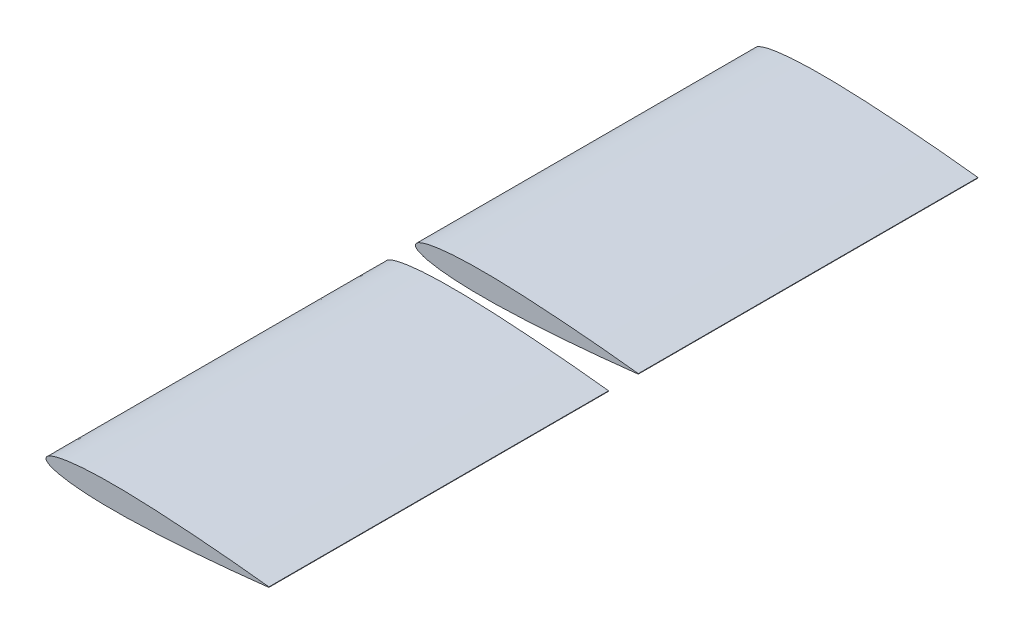
SolidWorks part; units mm, degrees
ref_plane "Спереди" through (0, 0, 0) normal (0, 0, 1) x (1, 0, 0)
ref_plane "Сверху" through (0, 0, 0) normal (0, 1, 0) x (1, 0, 0)
ref_plane "Справа" through (0, 0, 0) normal (1, 0, 0) x (0, 0, -1)
curve "Кривая2"
  spline degree 3 poles (210, 0.2205, 0) (209.4961, 0.2793, 0) (208.0885, 0.4434, 0) (205.5349, 0.7368, 0) (202.1573, 1.1183, 0) (198.2101, 1.5547, 0) (193.8164, 2.0291, 0) (189.059, 2.5297, 0) (184.0003, 3.0477, 0) (178.6905, 3.576, 0) (173.1712, 4.1089, 0) (167.4784, 4.6415, 0) (161.6434, 5.1696, 0) (155.6943, 5.6895, 0) (149.6563, 6.1979, 0) (143.5527, 6.6915, 0) (137.4046, 7.1675, 0) (131.2317, 7.6228, 0) (125.0525, 8.0547, 0) (118.8843, 8.4604, 0) (112.7433, 8.8371, 0) (106.645, 9.1821, 0) (100.604, 9.4927, 0) (94.6343, 9.7665, 0) (88.7492, 10.0009, 0) (82.9617, 10.1936, 0) (77.2839, 10.3425, 0) (71.7277, 10.4456, 0) (66.3046, 10.5012, 0) (61.0256, 10.5081, 0) (55.9013, 10.4648, 0) (50.9422, 10.3709, 0) (46.1583, 10.2257, 0) (41.5593, 10.0293, 0) (37.1549, 9.7819, 0) (32.9541, 9.4841, 0) (28.9661, 9.1368, 0) (25.1997, 8.7415, 0) (21.6633, 8.2995, 0) (18.3654, 7.8128, 0) (15.3141, 7.2834, 0) (12.5174, 6.7136, 0) (9.9828, 6.1055, 0) (7.7177, 5.4617, 0) (5.7292, 4.7844, 0) (4.0231, 4.0756, 0) (2.6063, 3.3369, 0) (1.4778, 2.5676, 0) (0.655, 1.7629, 0) (0.1057, 0.907, 0) (0.0341, 0.2924, 0) (0, 0, 0) knots 0 0 0 0 0.007145 0.019956 0.036196 0.055011 0.075879 0.098429 0.122376 0.147488 0.173572 0.20046 0.228005 0.256076 0.284555 0.313333 0.34231 0.371393 0.400496 0.429538 0.458442 0.487136 0.515552 0.543624 0.57129 0.598491 0.62517 0.651272 0.676746 0.701542 0.725611 0.748908 0.771388 0.793008 0.813728 0.833508 0.85231 0.870097 0.886836 0.902493 0.917037 0.930441 0.94268 0.953734 0.96359 0.972247 0.979722 0.986065 0.991385 0.995901 1 1 1 1
curve "Кривая4"
  spline degree 3 poles (0, 0, 0) (0.0341, -0.2924, 0) (0.1057, -0.907, 0) (0.655, -1.7629, 0) (1.4778, -2.5676, 0) (2.6063, -3.3369, 0) (4.0231, -4.0756, 0) (5.7292, -4.7844, 0) (7.7177, -5.4617, 0) (9.9828, -6.1055, 0) (12.5174, -6.7136, 0) (15.3141, -7.2834, 0) (18.3654, -7.8128, 0) (21.6633, -8.2995, 0) (25.1997, -8.7415, 0) (28.9661, -9.1368, 0) (32.9541, -9.4841, 0) (37.1549, -9.7819, 0) (41.5593, -10.0293, 0) (46.1583, -10.2257, 0) (50.9422, -10.3709, 0) (55.9013, -10.4648, 0) (61.0256, -10.5081, 0) (66.3046, -10.5012, 0) (71.7277, -10.4456, 0) (77.2839, -10.3425, 0) (82.9617, -10.1936, 0) (88.7492, -10.0009, 0) (94.6343, -9.7665, 0) (100.604, -9.4927, 0) (106.645, -9.1821, 0) (112.7433, -8.8371, 0) (118.8843, -8.4604, 0) (125.0525, -8.0547, 0) (131.2317, -7.6228, 0) (137.4046, -7.1675, 0) (143.5527, -6.6915, 0) (149.6563, -6.1979, 0) (155.6943, -5.6895, 0) (161.6434, -5.1696, 0) (167.4784, -4.6415, 0) (173.1712, -4.1089, 0) (178.6905, -3.576, 0) (184.0003, -3.0477, 0) (189.059, -2.5297, 0) (193.8164, -2.0291, 0) (198.2101, -1.5547, 0) (202.1573, -1.1183, 0) (205.5349, -0.7368, 0) (208.0885, -0.4434, 0) (209.4961, -0.2793, 0) (210, -0.2205, 0) knots 0 0 0 0 0.004099 0.008615 0.013935 0.020278 0.027753 0.03641 0.046266 0.05732 0.069559 0.082963 0.097507 0.113164 0.129903 0.14769 0.166492 0.186272 0.206992 0.228612 0.251092 0.274389 0.298458 0.323254 0.348728 0.37483 0.401509 0.42871 0.456376 0.484448 0.512864 0.541558 0.570462 0.599504 0.628607 0.65769 0.686667 0.715445 0.743924 0.771995 0.79954 0.826428 0.852512 0.877624 0.901571 0.924121 0.944989 0.963804 0.980044 0.992855 1 1 1 1
sketch "Эскиз6" plane through (0, 0, 0) normal (0, 0, 1) x (1, 0, 0)
  line L0 (210, 0.2205) -> (210, -0.2205)
  circle A0 centre (42, 0) radius 5
  circle A2 centre (27, 0) radius 5
  circle A3 centre (59, 0) radius 7.5
  circle A4 centre (78, 0) radius 7.5
  circle A5 centre (96, 0) radius 6.5
  circle A6 centre (112, 0) radius 5
  circle A7 centre (127, 0) radius 5
  circle A8 centre (142, 0) radius 5
  circle A9 centre (15, 0) radius 4
  spline S0 degree 3 poles (-2866.9483, -881.3764) (76.8054, 46.1091) (-5.7335, 8.1907) (0.655, -1.7629) (1.4778, -2.5676) (2.6063, -3.3369) (4.0231, -4.0756) (5.7292, -4.7844) (7.7177, -5.4617) (9.9828, -6.1055) (12.5174, -6.7136) (15.3141, -7.2834) (18.3654, -7.8128) (21.6633, -8.2995) (25.1997, -8.7415) (28.9661, -9.1368) (32.9541, -9.4841) (37.1549, -9.7819) (41.5593, -10.0293) (46.1583, -10.2257) (50.9422, -10.3709) (55.9013, -10.4648) (61.0256, -10.5081) (66.3046, -10.5012) (71.7277, -10.4456) (77.2839, -10.3425) (82.9617, -10.1936) (88.7492, -10.0009) (94.6343, -9.7665) (100.604, -9.4927) (106.645, -9.1821) (112.7433, -8.8371) (118.8843, -8.4604) (125.0525, -8.0547) (131.2317, -7.6228) (137.4046, -7.1675) (143.5527, -6.6915) (149.6563, -6.1979) (155.6943, -5.6895) (161.6434, -5.1696) (169.3231, -4.4745) (176.7905, -3.765) (184.0003, -3.0477) (189.059, -2.5297) (193.8164, -2.0291) (198.2101, -1.5547) (202.1573, -1.1183) (205.5349, -0.7368) (314.9698, 11.8352) (421.599, 38.5691) (873.4429, -2915.4445) knots -0.148126 -0.148126 -0.148126 -0.148126 0.004099 0.008615 0.013935 0.020278 0.027753 0.03641 0.046266 0.05732 0.069559 0.082963 0.097507 0.113164 0.129903 0.14769 0.166492 0.186272 0.206992 0.228612 0.251092 0.274389 0.298458 0.323254 0.348728 0.37483 0.401509 0.42871 0.456376 0.484448 0.512864 0.541558 0.570462 0.599504 0.628607 0.65769 0.686667 0.715445 0.743924 0.771995 0.79954 0.852512 0.877624 0.901571 0.924121 0.944989 0.963804 0.980044 0.992855 2.515013 2.515013 2.515013 2.515013 only from (0, 0) to (210, -0.2205) construction
  spline S1 degree 3 poles (873.4362, 2915.401) (421.598, -38.5689) (314.9692, -11.8351) (205.5349, 0.7368) (202.1573, 1.1183) (198.2101, 1.5547) (193.8164, 2.0291) (189.059, 2.5297) (184.0003, 3.0477) (176.7905, 3.765) (169.3231, 4.4745) (161.6434, 5.1696) (155.6943, 5.6895) (149.6563, 6.1979) (143.5527, 6.6915) (137.4046, 7.1675) (131.2317, 7.6228) (125.0525, 8.0547) (118.8843, 8.4604) (112.7433, 8.8371) (106.645, 9.1821) (100.604, 9.4927) (94.6343, 9.7665) (88.7492, 10.0009) (82.9617, 10.1936) (77.2839, 10.3425) (71.7277, 10.4456) (66.3046, 10.5012) (61.0256, 10.5081) (55.9013, 10.4648) (50.9422, 10.3709) (46.1583, 10.2257) (41.5593, 10.0293) (37.1549, 9.7819) (32.9541, 9.4841) (28.9661, 9.1368) (25.1997, 8.7415) (21.6633, 8.2995) (18.3654, 7.8128) (15.3141, 7.2834) (12.5174, 6.7136) (9.9828, 6.1055) (7.7177, 5.4617) (5.7292, 4.7844) (4.0231, 4.0756) (2.6063, 3.3369) (1.4778, 2.5676) (0.655, 1.7629) (-5.7332, -8.1903) (76.7984, -46.1059) (-2866.561, 881.2544) knots -1.515006 -1.515006 -1.515006 -1.515006 0.007145 0.019956 0.036196 0.055011 0.075879 0.098429 0.122376 0.147488 0.20046 0.228005 0.256076 0.284555 0.313333 0.34231 0.371393 0.400496 0.429538 0.458442 0.487136 0.515552 0.543624 0.57129 0.598491 0.62517 0.651272 0.676746 0.701542 0.725611 0.748908 0.771388 0.793008 0.813728 0.833508 0.85231 0.870097 0.886836 0.902493 0.917037 0.930441 0.94268 0.953734 0.96359 0.972247 0.979722 0.986065 0.991385 0.995901 1.148119 1.148119 1.148119 1.148119 only from (210, 0.2205) to (0, 0) construction
  spline S2 degree 3 poles (0, 0) (0.0341, -0.2924) (0.1057, -0.907) (0.655, -1.7629) (1.4778, -2.5676) (2.6063, -3.3369) (4.0231, -4.0756) (5.7292, -4.7844) (7.7177, -5.4617) (9.9828, -6.1055) (12.5174, -6.7136) (15.3141, -7.2834) (18.3654, -7.8128) (21.6633, -8.2995) (25.1997, -8.7415) (28.9661, -9.1368) (32.9541, -9.4841) (37.1549, -9.7819) (41.5593, -10.0293) (46.1583, -10.2257) (50.9422, -10.3709) (55.9013, -10.4648) (61.0256, -10.5081) (66.3046, -10.5012) (71.7277, -10.4456) (77.2839, -10.3425) (82.9617, -10.1936) (88.7492, -10.0009) (94.6343, -9.7665) (100.604, -9.4927) (106.645, -9.1821) (112.7433, -8.8371) (118.8843, -8.4604) (125.0525, -8.0547) (131.2317, -7.6228) (137.4046, -7.1675) (143.5527, -6.6915) (149.6563, -6.1979) (155.6943, -5.6895) (161.6434, -5.1696) (169.3231, -4.4745) (176.7905, -3.765) (184.0003, -3.0477) (189.059, -2.5297) (193.8164, -2.0291) (198.2101, -1.5547) (202.1573, -1.1183) (205.5349, -0.7368) (208.0885, -0.4434) (209.4961, -0.2793) (210, -0.2205) knots 0 0 0 0 0.004099 0.008615 0.013935 0.020278 0.027753 0.03641 0.046266 0.05732 0.069559 0.082963 0.097507 0.113164 0.129903 0.14769 0.166492 0.186272 0.206992 0.228612 0.251092 0.274389 0.298458 0.323254 0.348728 0.37483 0.401509 0.42871 0.456376 0.484448 0.512864 0.541558 0.570462 0.599504 0.628607 0.65769 0.686667 0.715445 0.743924 0.771995 0.79954 0.852512 0.877624 0.901571 0.924121 0.944989 0.963804 0.980044 0.992855 1 1 1 1
  spline S3 degree 3 poles (210, 0.2205) (209.4961, 0.2793) (208.0885, 0.4434) (205.5349, 0.7368) (202.1573, 1.1183) (198.2101, 1.5547) (193.8164, 2.0291) (189.059, 2.5297) (184.0003, 3.0477) (176.7905, 3.765) (169.3231, 4.4745) (161.6434, 5.1696) (155.6943, 5.6895) (149.6563, 6.1979) (143.5527, 6.6915) (137.4046, 7.1675) (131.2317, 7.6228) (125.0525, 8.0547) (118.8843, 8.4604) (112.7433, 8.8371) (106.645, 9.1821) (100.604, 9.4927) (94.6343, 9.7665) (88.7492, 10.0009) (82.9617, 10.1936) (77.2839, 10.3425) (71.7277, 10.4456) (66.3046, 10.5012) (61.0256, 10.5081) (55.9013, 10.4648) (50.9422, 10.3709) (46.1583, 10.2257) (41.5593, 10.0293) (37.1549, 9.7819) (32.9541, 9.4841) (28.9661, 9.1368) (25.1997, 8.7415) (21.6633, 8.2995) (18.3654, 7.8128) (15.3141, 7.2834) (12.5174, 6.7136) (9.9828, 6.1055) (7.7177, 5.4617) (5.7292, 4.7844) (4.0231, 4.0756) (2.6063, 3.3369) (1.4778, 2.5676) (0.655, 1.7629) (0.1057, 0.907) (0.0341, 0.2924) (0, 0) knots 0 0 0 0 0.007145 0.019956 0.036196 0.055011 0.075879 0.098429 0.122376 0.147488 0.20046 0.228005 0.256076 0.284555 0.313333 0.34231 0.371393 0.400496 0.429538 0.458442 0.487136 0.515552 0.543624 0.57129 0.598491 0.62517 0.651272 0.676746 0.701542 0.725611 0.748908 0.771388 0.793008 0.813728 0.833508 0.85231 0.870097 0.886836 0.902493 0.917037 0.930441 0.94268 0.953734 0.96359 0.972247 0.979722 0.986065 0.991385 0.995901 1 1 1 1
  dimension "D1" = 10
  dimension "D3" = 10
  dimension "D4" = 15
  dimension "D5" = 15
  dimension "D6" = 13
  dimension "D7" = 10
  dimension "D15" = 10
  dimension "D16" = 10
  dimension "D17" = 8
  dimension "D2" = 42
  dimension "D8" = 27
  dimension "D9" = 59
  dimension "D10" = 78
  dimension "D11" = 96
  dimension "D12" = 112
  dimension "D13" = 127
  dimension "D14" = 142
  dimension "D18" = 15
ref_plane "л2" through (0, 0, 170) normal (0, 0, 1) x (1, 0, 0)
ref_plane "п2" through (0, 0, -170) normal (0, 0, 1) x (1, 0, 0)
ref_plane "п3" through (0, 0, -334) normal (0, 0, 1) x (1, 0, 0)
ref_plane "л3" through (0, 0, 334) normal (0, 0, 1) x (1, 0, 0)
ref_axis "Ось1" through (0, 0, -345.1687) along (0, 0, 1)
sketch "нерв л2" plane through (0, 0, 170) normal (0, 0, 1) x (1, 0, 0)
  line L0 (210, 0.2205) -> (210, -0.2205)
  circle A0 centre (42, 0) radius 5
  circle A2 centre (27, 0) radius 5
  circle A3 centre (59, 0) radius 7.5
  circle A4 centre (78, 0) radius 7.5
  circle A5 centre (96, 0) radius 6.5
  circle A6 centre (112, 0) radius 5
  circle A7 centre (127, 0) radius 5
  circle A8 centre (142, 0) radius 5
  circle A9 centre (15, 0) radius 4
  spline S2 degree 3 poles (0, 0) (0.0341, -0.2924) (0.1057, -0.907) (0.655, -1.7629) (1.4778, -2.5676) (2.6063, -3.3369) (4.0231, -4.0756) (5.7292, -4.7844) (7.7177, -5.4617) (9.9828, -6.1055) (12.5174, -6.7136) (15.3141, -7.2834) (18.3654, -7.8128) (21.6633, -8.2995) (25.1997, -8.7415) (28.9661, -9.1368) (32.9541, -9.4841) (37.1549, -9.7819) (41.5593, -10.0293) (46.1583, -10.2257) (50.9422, -10.3709) (55.9013, -10.4648) (61.0256, -10.5081) (66.3046, -10.5012) (71.7277, -10.4456) (77.2839, -10.3425) (82.9617, -10.1936) (88.7492, -10.0009) (94.6343, -9.7665) (100.604, -9.4927) (106.645, -9.1821) (112.7433, -8.8371) (118.8843, -8.4604) (125.0525, -8.0547) (131.2317, -7.6228) (137.4046, -7.1675) (143.5527, -6.6915) (149.6563, -6.1979) (155.6943, -5.6895) (161.6434, -5.1696) (169.3231, -4.4745) (176.7905, -3.765) (184.0003, -3.0477) (189.059, -2.5297) (193.8164, -2.0291) (198.2101, -1.5547) (202.1573, -1.1183) (205.5349, -0.7368) (208.0885, -0.4434) (209.4961, -0.2793) (210, -0.2205) knots 0 0 0 0 0.004099 0.008615 0.013935 0.020278 0.027753 0.03641 0.046266 0.05732 0.069559 0.082963 0.097507 0.113164 0.129903 0.14769 0.166492 0.186272 0.206992 0.228612 0.251092 0.274389 0.298458 0.323254 0.348728 0.37483 0.401509 0.42871 0.456376 0.484448 0.512864 0.541558 0.570462 0.599504 0.628607 0.65769 0.686667 0.715445 0.743924 0.771995 0.79954 0.852512 0.877624 0.901571 0.924121 0.944989 0.963804 0.980044 0.992855 1 1 1 1
  spline S3 degree 3 poles (210, 0.2205) (209.4961, 0.2793) (208.0885, 0.4434) (205.5349, 0.7368) (202.1573, 1.1183) (198.2101, 1.5547) (193.8164, 2.0291) (189.059, 2.5297) (184.0003, 3.0477) (176.7905, 3.765) (169.3231, 4.4745) (161.6434, 5.1696) (155.6943, 5.6895) (149.6563, 6.1979) (143.5527, 6.6915) (137.4046, 7.1675) (131.2317, 7.6228) (125.0525, 8.0547) (118.8843, 8.4604) (112.7433, 8.8371) (106.645, 9.1821) (100.604, 9.4927) (94.6343, 9.7665) (88.7492, 10.0009) (82.9617, 10.1936) (77.2839, 10.3425) (71.7277, 10.4456) (66.3046, 10.5012) (61.0256, 10.5081) (55.9013, 10.4648) (50.9422, 10.3709) (46.1583, 10.2257) (41.5593, 10.0293) (37.1549, 9.7819) (32.9541, 9.4841) (28.9661, 9.1368) (25.1997, 8.7415) (21.6633, 8.2995) (18.3654, 7.8128) (15.3141, 7.2834) (12.5174, 6.7136) (9.9828, 6.1055) (7.7177, 5.4617) (5.7292, 4.7844) (4.0231, 4.0756) (2.6063, 3.3369) (1.4778, 2.5676) (0.655, 1.7629) (0.1057, 0.907) (0.0341, 0.2924) (0, 0) knots 0 0 0 0 0.007145 0.019956 0.036196 0.055011 0.075879 0.098429 0.122376 0.147488 0.20046 0.228005 0.256076 0.284555 0.313333 0.34231 0.371393 0.400496 0.429538 0.458442 0.487136 0.515552 0.543624 0.57129 0.598491 0.62517 0.651272 0.676746 0.701542 0.725611 0.748908 0.771388 0.793008 0.813728 0.833508 0.85231 0.870097 0.886836 0.902493 0.917037 0.930441 0.94268 0.953734 0.96359 0.972247 0.979722 0.986065 0.991385 0.995901 1 1 1 1
  dimension "D1" = 10
  dimension "D3" = 10
  dimension "D4" = 15
  dimension "D5" = 15
  dimension "D6" = 13
  dimension "D7" = 10
  dimension "D15" = 10
  dimension "D16" = 10
  dimension "D17" = 8
  dimension "D2" = 42
  dimension "D8" = 27
  dimension "D9" = 59
  dimension "D10" = 78
  dimension "D11" = 96
  dimension "D12" = 112
  dimension "D13" = 127
  dimension "D14" = 142
  dimension "D18" = 15
  dimension "D19" = 210
  dimension "D20" = 0.441
  dimension "D21" = 0.2205
sketch "нерв п2" plane through (0, 0, -170) normal (0, 0, 1) x (1, 0, 0)
  line L0 (210, 0.2205) -> (210, -0.2205)
  circle A0 centre (42, 0) radius 5
  circle A2 centre (27, 0) radius 5
  circle A3 centre (59, 0) radius 7.5
  circle A4 centre (78, 0) radius 7.5
  circle A5 centre (96, 0) radius 6.5
  circle A6 centre (112, 0) radius 5
  circle A7 centre (127, 0) radius 5
  circle A8 centre (142, 0) radius 5
  circle A9 centre (15, 0) radius 4
  spline S2 degree 3 poles (0, 0) (0.0341, -0.2924) (0.1057, -0.907) (0.655, -1.7629) (1.4778, -2.5676) (2.6063, -3.3369) (4.0231, -4.0756) (5.7292, -4.7844) (7.7177, -5.4617) (9.9828, -6.1055) (12.5174, -6.7136) (15.3141, -7.2834) (18.3654, -7.8128) (21.6633, -8.2995) (25.1997, -8.7415) (28.9661, -9.1368) (32.9541, -9.4841) (37.1549, -9.7819) (41.5593, -10.0293) (46.1583, -10.2257) (50.9422, -10.3709) (55.9013, -10.4648) (61.0256, -10.5081) (66.3046, -10.5012) (71.7277, -10.4456) (77.2839, -10.3425) (82.9617, -10.1936) (88.7492, -10.0009) (94.6343, -9.7665) (100.604, -9.4927) (106.645, -9.1821) (112.7433, -8.8371) (118.8843, -8.4604) (125.0525, -8.0547) (131.2317, -7.6228) (137.4046, -7.1675) (143.5527, -6.6915) (149.6563, -6.1979) (155.6943, -5.6895) (161.6434, -5.1696) (169.3231, -4.4745) (176.7905, -3.765) (184.0003, -3.0477) (189.059, -2.5297) (193.8164, -2.0291) (198.2101, -1.5547) (202.1573, -1.1183) (205.5349, -0.7368) (208.0885, -0.4434) (209.4961, -0.2793) (210, -0.2205) knots 0 0 0 0 0.004099 0.008615 0.013935 0.020278 0.027753 0.03641 0.046266 0.05732 0.069559 0.082963 0.097507 0.113164 0.129903 0.14769 0.166492 0.186272 0.206992 0.228612 0.251092 0.274389 0.298458 0.323254 0.348728 0.37483 0.401509 0.42871 0.456376 0.484448 0.512864 0.541558 0.570462 0.599504 0.628607 0.65769 0.686667 0.715445 0.743924 0.771995 0.79954 0.852512 0.877624 0.901571 0.924121 0.944989 0.963804 0.980044 0.992855 1 1 1 1
  spline S3 degree 3 poles (210, 0.2205) (209.4961, 0.2793) (208.0885, 0.4434) (205.5349, 0.7368) (202.1573, 1.1183) (198.2101, 1.5547) (193.8164, 2.0291) (189.059, 2.5297) (184.0003, 3.0477) (176.7905, 3.765) (169.3231, 4.4745) (161.6434, 5.1696) (155.6943, 5.6895) (149.6563, 6.1979) (143.5527, 6.6915) (137.4046, 7.1675) (131.2317, 7.6228) (125.0525, 8.0547) (118.8843, 8.4604) (112.7433, 8.8371) (106.645, 9.1821) (100.604, 9.4927) (94.6343, 9.7665) (88.7492, 10.0009) (82.9617, 10.1936) (77.2839, 10.3425) (71.7277, 10.4456) (66.3046, 10.5012) (61.0256, 10.5081) (55.9013, 10.4648) (50.9422, 10.3709) (46.1583, 10.2257) (41.5593, 10.0293) (37.1549, 9.7819) (32.9541, 9.4841) (28.9661, 9.1368) (25.1997, 8.7415) (21.6633, 8.2995) (18.3654, 7.8128) (15.3141, 7.2834) (12.5174, 6.7136) (9.9828, 6.1055) (7.7177, 5.4617) (5.7292, 4.7844) (4.0231, 4.0756) (2.6063, 3.3369) (1.4778, 2.5676) (0.655, 1.7629) (0.1057, 0.907) (0.0341, 0.2924) (0, 0) knots 0 0 0 0 0.007145 0.019956 0.036196 0.055011 0.075879 0.098429 0.122376 0.147488 0.20046 0.228005 0.256076 0.284555 0.313333 0.34231 0.371393 0.400496 0.429538 0.458442 0.487136 0.515552 0.543624 0.57129 0.598491 0.62517 0.651272 0.676746 0.701542 0.725611 0.748908 0.771388 0.793008 0.813728 0.833508 0.85231 0.870097 0.886836 0.902493 0.917037 0.930441 0.94268 0.953734 0.96359 0.972247 0.979722 0.986065 0.991385 0.995901 1 1 1 1
  dimension "D1" = 10
  dimension "D3" = 10
  dimension "D4" = 15
  dimension "D5" = 15
  dimension "D6" = 13
  dimension "D7" = 10
  dimension "D15" = 10
  dimension "D16" = 10
  dimension "D17" = 8
  dimension "D2" = 42
  dimension "D8" = 27
  dimension "D9" = 59
  dimension "D10" = 78
  dimension "D11" = 96
  dimension "D12" = 112
  dimension "D13" = 127
  dimension "D14" = 142
  dimension "D18" = 15
  dimension "D19" = 210
  dimension "D20" = 0.441
  dimension "D21" = 0.2205
sketch "нерв п3" plane through (0, 0, -334) normal (0, 0, 1) x (1, 0, 0)
  line L0 (210, 0.2205) -> (210, -0.2205)
  circle A0 centre (42, 0) radius 5
  circle A2 centre (27, 0) radius 5
  circle A3 centre (59, 0) radius 7.5
  circle A4 centre (78, 0) radius 7.5
  circle A5 centre (96, 0) radius 6.5
  circle A6 centre (112, 0) radius 5
  circle A7 centre (127, 0) radius 5
  circle A8 centre (142, 0) radius 5
  circle A9 centre (15, 0) radius 4
  spline S2 degree 3 poles (0, 0) (0.0341, -0.2924) (0.1057, -0.907) (0.655, -1.7629) (1.4778, -2.5676) (2.6063, -3.3369) (4.0231, -4.0756) (5.7292, -4.7844) (7.7177, -5.4617) (9.9828, -6.1055) (12.5174, -6.7136) (15.3141, -7.2834) (18.3654, -7.8128) (21.6633, -8.2995) (25.1997, -8.7415) (28.9661, -9.1368) (32.9541, -9.4841) (37.1549, -9.7819) (41.5593, -10.0293) (46.1583, -10.2257) (50.9422, -10.3709) (55.9013, -10.4648) (61.0256, -10.5081) (66.3046, -10.5012) (71.7277, -10.4456) (77.2839, -10.3425) (82.9617, -10.1936) (88.7492, -10.0009) (94.6343, -9.7665) (100.604, -9.4927) (106.645, -9.1821) (112.7433, -8.8371) (118.8843, -8.4604) (125.0525, -8.0547) (131.2317, -7.6228) (137.4046, -7.1675) (143.5527, -6.6915) (149.6563, -6.1979) (155.6943, -5.6895) (161.6434, -5.1696) (169.3231, -4.4745) (176.7905, -3.765) (184.0003, -3.0477) (189.059, -2.5297) (193.8164, -2.0291) (198.2101, -1.5547) (202.1573, -1.1183) (205.5349, -0.7368) (208.0885, -0.4434) (209.4961, -0.2793) (210, -0.2205) knots 0 0 0 0 0.004099 0.008615 0.013935 0.020278 0.027753 0.03641 0.046266 0.05732 0.069559 0.082963 0.097507 0.113164 0.129903 0.14769 0.166492 0.186272 0.206992 0.228612 0.251092 0.274389 0.298458 0.323254 0.348728 0.37483 0.401509 0.42871 0.456376 0.484448 0.512864 0.541558 0.570462 0.599504 0.628607 0.65769 0.686667 0.715445 0.743924 0.771995 0.79954 0.852512 0.877624 0.901571 0.924121 0.944989 0.963804 0.980044 0.992855 1 1 1 1
  spline S3 degree 3 poles (210, 0.2205) (209.4961, 0.2793) (208.0885, 0.4434) (205.5349, 0.7368) (202.1573, 1.1183) (198.2101, 1.5547) (193.8164, 2.0291) (189.059, 2.5297) (184.0003, 3.0477) (176.7905, 3.765) (169.3231, 4.4745) (161.6434, 5.1696) (155.6943, 5.6895) (149.6563, 6.1979) (143.5527, 6.6915) (137.4046, 7.1675) (131.2317, 7.6228) (125.0525, 8.0547) (118.8843, 8.4604) (112.7433, 8.8371) (106.645, 9.1821) (100.604, 9.4927) (94.6343, 9.7665) (88.7492, 10.0009) (82.9617, 10.1936) (77.2839, 10.3425) (71.7277, 10.4456) (66.3046, 10.5012) (61.0256, 10.5081) (55.9013, 10.4648) (50.9422, 10.3709) (46.1583, 10.2257) (41.5593, 10.0293) (37.1549, 9.7819) (32.9541, 9.4841) (28.9661, 9.1368) (25.1997, 8.7415) (21.6633, 8.2995) (18.3654, 7.8128) (15.3141, 7.2834) (12.5174, 6.7136) (9.9828, 6.1055) (7.7177, 5.4617) (5.7292, 4.7844) (4.0231, 4.0756) (2.6063, 3.3369) (1.4778, 2.5676) (0.655, 1.7629) (0.1057, 0.907) (0.0341, 0.2924) (0, 0) knots 0 0 0 0 0.007145 0.019956 0.036196 0.055011 0.075879 0.098429 0.122376 0.147488 0.20046 0.228005 0.256076 0.284555 0.313333 0.34231 0.371393 0.400496 0.429538 0.458442 0.487136 0.515552 0.543624 0.57129 0.598491 0.62517 0.651272 0.676746 0.701542 0.725611 0.748908 0.771388 0.793008 0.813728 0.833508 0.85231 0.870097 0.886836 0.902493 0.917037 0.930441 0.94268 0.953734 0.96359 0.972247 0.979722 0.986065 0.991385 0.995901 1 1 1 1
  dimension "D1" = 10
  dimension "D3" = 10
  dimension "D4" = 15
  dimension "D5" = 15
  dimension "D6" = 13
  dimension "D7" = 10
  dimension "D15" = 10
  dimension "D16" = 10
  dimension "D17" = 8
  dimension "D2" = 42
  dimension "D8" = 27
  dimension "D9" = 59
  dimension "D10" = 78
  dimension "D11" = 96
  dimension "D12" = 112
  dimension "D13" = 127
  dimension "D14" = 142
  dimension "D18" = 15
  dimension "D19" = 210
  dimension "D20" = 0.2205
  dimension "D21" = 0.441
sketch "нерв л3" plane through (0, 0, 334) normal (0, 0, 1) x (1, 0, 0)
  line L0 (210, 0.2205) -> (210, -0.2205)
  circle A0 centre (42, 0) radius 5
  circle A2 centre (27, 0) radius 5
  circle A3 centre (59, 0) radius 7.5
  circle A4 centre (78, 0) radius 7.5
  circle A5 centre (96, 0) radius 6.5
  circle A6 centre (112, 0) radius 5
  circle A7 centre (127, 0) radius 5
  circle A8 centre (142, 0) radius 5
  circle A9 centre (15, 0) radius 4
  spline S2 degree 3 poles (0, 0) (0.0341, -0.2924) (0.1057, -0.907) (0.655, -1.7629) (1.4778, -2.5676) (2.6063, -3.3369) (4.0231, -4.0756) (5.7292, -4.7844) (7.7177, -5.4617) (9.9828, -6.1055) (12.5174, -6.7136) (15.3141, -7.2834) (18.3654, -7.8128) (21.6633, -8.2995) (25.1997, -8.7415) (28.9661, -9.1368) (32.9541, -9.4841) (37.1549, -9.7819) (41.5593, -10.0293) (46.1583, -10.2257) (50.9422, -10.3709) (55.9013, -10.4648) (61.0256, -10.5081) (66.3046, -10.5012) (71.7277, -10.4456) (77.2839, -10.3425) (82.9617, -10.1936) (88.7492, -10.0009) (94.6343, -9.7665) (100.604, -9.4927) (106.645, -9.1821) (112.7433, -8.8371) (118.8843, -8.4604) (125.0525, -8.0547) (131.2317, -7.6228) (137.4046, -7.1675) (143.5527, -6.6915) (149.6563, -6.1979) (155.6943, -5.6895) (161.6434, -5.1696) (169.3231, -4.4745) (176.7905, -3.765) (184.0003, -3.0477) (189.059, -2.5297) (193.8164, -2.0291) (198.2101, -1.5547) (202.1573, -1.1183) (205.5349, -0.7368) (208.0885, -0.4434) (209.4961, -0.2793) (210, -0.2205) knots 0 0 0 0 0.004099 0.008615 0.013935 0.020278 0.027753 0.03641 0.046266 0.05732 0.069559 0.082963 0.097507 0.113164 0.129903 0.14769 0.166492 0.186272 0.206992 0.228612 0.251092 0.274389 0.298458 0.323254 0.348728 0.37483 0.401509 0.42871 0.456376 0.484448 0.512864 0.541558 0.570462 0.599504 0.628607 0.65769 0.686667 0.715445 0.743924 0.771995 0.79954 0.852512 0.877624 0.901571 0.924121 0.944989 0.963804 0.980044 0.992855 1 1 1 1
  spline S3 degree 3 poles (210, 0.2205) (209.4961, 0.2793) (208.0885, 0.4434) (205.5349, 0.7368) (202.1573, 1.1183) (198.2101, 1.5547) (193.8164, 2.0291) (189.059, 2.5297) (184.0003, 3.0477) (176.7905, 3.765) (169.3231, 4.4745) (161.6434, 5.1696) (155.6943, 5.6895) (149.6563, 6.1979) (143.5527, 6.6915) (137.4046, 7.1675) (131.2317, 7.6228) (125.0525, 8.0547) (118.8843, 8.4604) (112.7433, 8.8371) (106.645, 9.1821) (100.604, 9.4927) (94.6343, 9.7665) (88.7492, 10.0009) (82.9617, 10.1936) (77.2839, 10.3425) (71.7277, 10.4456) (66.3046, 10.5012) (61.0256, 10.5081) (55.9013, 10.4648) (50.9422, 10.3709) (46.1583, 10.2257) (41.5593, 10.0293) (37.1549, 9.7819) (32.9541, 9.4841) (28.9661, 9.1368) (25.1997, 8.7415) (21.6633, 8.2995) (18.3654, 7.8128) (15.3141, 7.2834) (12.5174, 6.7136) (9.9828, 6.1055) (7.7177, 5.4617) (5.7292, 4.7844) (4.0231, 4.0756) (2.6063, 3.3369) (1.4778, 2.5676) (0.655, 1.7629) (0.1057, 0.907) (0.0341, 0.2924) (0, 0) knots 0 0 0 0 0.007145 0.019956 0.036196 0.055011 0.075879 0.098429 0.122376 0.147488 0.20046 0.228005 0.256076 0.284555 0.313333 0.34231 0.371393 0.400496 0.429538 0.458442 0.487136 0.515552 0.543624 0.57129 0.598491 0.62517 0.651272 0.676746 0.701542 0.725611 0.748908 0.771388 0.793008 0.813728 0.833508 0.85231 0.870097 0.886836 0.902493 0.917037 0.930441 0.94268 0.953734 0.96359 0.972247 0.979722 0.986065 0.991385 0.995901 1 1 1 1
  dimension "D1" = 10
  dimension "D3" = 10
  dimension "D4" = 15
  dimension "D5" = 15
  dimension "D6" = 13
  dimension "D7" = 10
  dimension "D15" = 10
  dimension "D16" = 10
  dimension "D17" = 8
  dimension "D2" = 42
  dimension "D8" = 27
  dimension "D9" = 59
  dimension "D10" = 78
  dimension "D11" = 96
  dimension "D12" = 112
  dimension "D13" = 127
  dimension "D14" = 142
  dimension "D18" = 15
  dimension "D19" = 210
  dimension "D20" = 0.2205
  dimension "D21" = 0.441
ref_plane "л1" through (0, 0, 14) normal (0, 0, 1) x (1, 0, 0)
ref_plane "п1" through (0, 0, -14) normal (0, 0, 1) x (1, 0, 0)
sketch "нерв л1" plane through (0, 0, 14) normal (0, 0, 1) x (1, 0, 0)
  line L0 (210, 0.2205) -> (210, -0.2205)
  circle A0 centre (42, 0) radius 5
  circle A2 centre (27, 0) radius 5
  circle A3 centre (59, 0) radius 7.5
  circle A4 centre (78, 0) radius 7.5
  circle A5 centre (96, 0) radius 6.5
  circle A6 centre (112, 0) radius 5
  circle A7 centre (127, 0) radius 5
  circle A8 centre (142, 0) radius 5
  circle A9 centre (15, 0) radius 4
  spline S2 degree 3 poles (0, 0) (0.0341, -0.2924) (0.1057, -0.907) (0.655, -1.7629) (1.4778, -2.5676) (2.6063, -3.3369) (4.0231, -4.0756) (5.7292, -4.7844) (7.7177, -5.4617) (9.9828, -6.1055) (12.5174, -6.7136) (15.3141, -7.2834) (18.3654, -7.8128) (21.6633, -8.2995) (25.1997, -8.7415) (28.9661, -9.1368) (32.9541, -9.4841) (37.1549, -9.7819) (41.5593, -10.0293) (46.1583, -10.2257) (50.9422, -10.3709) (55.9013, -10.4648) (61.0256, -10.5081) (66.3046, -10.5012) (71.7277, -10.4456) (77.2839, -10.3425) (82.9617, -10.1936) (88.7492, -10.0009) (94.6343, -9.7665) (100.604, -9.4927) (106.645, -9.1821) (112.7433, -8.8371) (118.8843, -8.4604) (125.0525, -8.0547) (131.2317, -7.6228) (137.4046, -7.1675) (143.5527, -6.6915) (149.6563, -6.1979) (155.6943, -5.6895) (161.6434, -5.1696) (169.3231, -4.4745) (176.7905, -3.765) (184.0003, -3.0477) (189.059, -2.5297) (193.8164, -2.0291) (198.2101, -1.5547) (202.1573, -1.1183) (205.5349, -0.7368) (208.0885, -0.4434) (209.4961, -0.2793) (210, -0.2205) knots 0 0 0 0 0.004099 0.008615 0.013935 0.020278 0.027753 0.03641 0.046266 0.05732 0.069559 0.082963 0.097507 0.113164 0.129903 0.14769 0.166492 0.186272 0.206992 0.228612 0.251092 0.274389 0.298458 0.323254 0.348728 0.37483 0.401509 0.42871 0.456376 0.484448 0.512864 0.541558 0.570462 0.599504 0.628607 0.65769 0.686667 0.715445 0.743924 0.771995 0.79954 0.852512 0.877624 0.901571 0.924121 0.944989 0.963804 0.980044 0.992855 1 1 1 1
  spline S3 degree 3 poles (210, 0.2205) (209.4961, 0.2793) (208.0885, 0.4434) (205.5349, 0.7368) (202.1573, 1.1183) (198.2101, 1.5547) (193.8164, 2.0291) (189.059, 2.5297) (184.0003, 3.0477) (176.7905, 3.765) (169.3231, 4.4745) (161.6434, 5.1696) (155.6943, 5.6895) (149.6563, 6.1979) (143.5527, 6.6915) (137.4046, 7.1675) (131.2317, 7.6228) (125.0525, 8.0547) (118.8843, 8.4604) (112.7433, 8.8371) (106.645, 9.1821) (100.604, 9.4927) (94.6343, 9.7665) (88.7492, 10.0009) (82.9617, 10.1936) (77.2839, 10.3425) (71.7277, 10.4456) (66.3046, 10.5012) (61.0256, 10.5081) (55.9013, 10.4648) (50.9422, 10.3709) (46.1583, 10.2257) (41.5593, 10.0293) (37.1549, 9.7819) (32.9541, 9.4841) (28.9661, 9.1368) (25.1997, 8.7415) (21.6633, 8.2995) (18.3654, 7.8128) (15.3141, 7.2834) (12.5174, 6.7136) (9.9828, 6.1055) (7.7177, 5.4617) (5.7292, 4.7844) (4.0231, 4.0756) (2.6063, 3.3369) (1.4778, 2.5676) (0.655, 1.7629) (0.1057, 0.907) (0.0341, 0.2924) (0, 0) knots 0 0 0 0 0.007145 0.019956 0.036196 0.055011 0.075879 0.098429 0.122376 0.147488 0.20046 0.228005 0.256076 0.284555 0.313333 0.34231 0.371393 0.400496 0.429538 0.458442 0.487136 0.515552 0.543624 0.57129 0.598491 0.62517 0.651272 0.676746 0.701542 0.725611 0.748908 0.771388 0.793008 0.813728 0.833508 0.85231 0.870097 0.886836 0.902493 0.917037 0.930441 0.94268 0.953734 0.96359 0.972247 0.979722 0.986065 0.991385 0.995901 1 1 1 1
  dimension "D1" = 10
  dimension "D3" = 10
  dimension "D4" = 15
  dimension "D5" = 15
  dimension "D6" = 13
  dimension "D7" = 10
  dimension "D15" = 10
  dimension "D16" = 10
  dimension "D17" = 8
  dimension "D2" = 42
  dimension "D8" = 27
  dimension "D9" = 59
  dimension "D10" = 78
  dimension "D11" = 96
  dimension "D12" = 112
  dimension "D13" = 127
  dimension "D14" = 142
  dimension "D18" = 15
  dimension "D19" = 210
  dimension "D20" = 0.2205
  dimension "D21" = 0.441
sketch "нерв п1" plane through (0, 0, -14) normal (0, 0, 1) x (1, 0, 0)
  line L0 (210, 0.2205) -> (210, -0.2205)
  circle A0 centre (42, 0) radius 5
  circle A2 centre (27, 0) radius 5
  circle A3 centre (59, 0) radius 7.5
  circle A4 centre (78, 0) radius 7.5
  circle A5 centre (96, 0) radius 6.5
  circle A6 centre (112, 0) radius 5
  circle A7 centre (127, 0) radius 5
  circle A8 centre (142, 0) radius 5
  circle A9 centre (15, 0) radius 4
  spline S2 degree 3 poles (0, 0) (0.0341, -0.2924) (0.1057, -0.907) (0.655, -1.7629) (1.4778, -2.5676) (2.6063, -3.3369) (4.0231, -4.0756) (5.7292, -4.7844) (7.7177, -5.4617) (9.9828, -6.1055) (12.5174, -6.7136) (15.3141, -7.2834) (18.3654, -7.8128) (21.6633, -8.2995) (25.1997, -8.7415) (28.9661, -9.1368) (32.9541, -9.4841) (37.1549, -9.7819) (41.5593, -10.0293) (46.1583, -10.2257) (50.9422, -10.3709) (55.9013, -10.4648) (61.0256, -10.5081) (66.3046, -10.5012) (71.7277, -10.4456) (77.2839, -10.3425) (82.9617, -10.1936) (88.7492, -10.0009) (94.6343, -9.7665) (100.604, -9.4927) (106.645, -9.1821) (112.7433, -8.8371) (118.8843, -8.4604) (125.0525, -8.0547) (131.2317, -7.6228) (137.4046, -7.1675) (143.5527, -6.6915) (149.6563, -6.1979) (155.6943, -5.6895) (161.6434, -5.1696) (169.3231, -4.4745) (176.7905, -3.765) (184.0003, -3.0477) (189.059, -2.5297) (193.8164, -2.0291) (198.2101, -1.5547) (202.1573, -1.1183) (205.5349, -0.7368) (208.0885, -0.4434) (209.4961, -0.2793) (210, -0.2205) knots 0 0 0 0 0.004099 0.008615 0.013935 0.020278 0.027753 0.03641 0.046266 0.05732 0.069559 0.082963 0.097507 0.113164 0.129903 0.14769 0.166492 0.186272 0.206992 0.228612 0.251092 0.274389 0.298458 0.323254 0.348728 0.37483 0.401509 0.42871 0.456376 0.484448 0.512864 0.541558 0.570462 0.599504 0.628607 0.65769 0.686667 0.715445 0.743924 0.771995 0.79954 0.852512 0.877624 0.901571 0.924121 0.944989 0.963804 0.980044 0.992855 1 1 1 1
  spline S3 degree 3 poles (210, 0.2205) (209.4961, 0.2793) (208.0885, 0.4434) (205.5349, 0.7368) (202.1573, 1.1183) (198.2101, 1.5547) (193.8164, 2.0291) (189.059, 2.5297) (184.0003, 3.0477) (176.7905, 3.765) (169.3231, 4.4745) (161.6434, 5.1696) (155.6943, 5.6895) (149.6563, 6.1979) (143.5527, 6.6915) (137.4046, 7.1675) (131.2317, 7.6228) (125.0525, 8.0547) (118.8843, 8.4604) (112.7433, 8.8371) (106.645, 9.1821) (100.604, 9.4927) (94.6343, 9.7665) (88.7492, 10.0009) (82.9617, 10.1936) (77.2839, 10.3425) (71.7277, 10.4456) (66.3046, 10.5012) (61.0256, 10.5081) (55.9013, 10.4648) (50.9422, 10.3709) (46.1583, 10.2257) (41.5593, 10.0293) (37.1549, 9.7819) (32.9541, 9.4841) (28.9661, 9.1368) (25.1997, 8.7415) (21.6633, 8.2995) (18.3654, 7.8128) (15.3141, 7.2834) (12.5174, 6.7136) (9.9828, 6.1055) (7.7177, 5.4617) (5.7292, 4.7844) (4.0231, 4.0756) (2.6063, 3.3369) (1.4778, 2.5676) (0.655, 1.7629) (0.1057, 0.907) (0.0341, 0.2924) (0, 0) knots 0 0 0 0 0.007145 0.019956 0.036196 0.055011 0.075879 0.098429 0.122376 0.147488 0.20046 0.228005 0.256076 0.284555 0.313333 0.34231 0.371393 0.400496 0.429538 0.458442 0.487136 0.515552 0.543624 0.57129 0.598491 0.62517 0.651272 0.676746 0.701542 0.725611 0.748908 0.771388 0.793008 0.813728 0.833508 0.85231 0.870097 0.886836 0.902493 0.917037 0.930441 0.94268 0.953734 0.96359 0.972247 0.979722 0.986065 0.991385 0.995901 1 1 1 1
  dimension "D1" = 10
  dimension "D3" = 10
  dimension "D4" = 15
  dimension "D5" = 15
  dimension "D6" = 13
  dimension "D7" = 10
  dimension "D15" = 10
  dimension "D16" = 10
  dimension "D17" = 8
  dimension "D2" = 42
  dimension "D8" = 27
  dimension "D9" = 59
  dimension "D10" = 78
  dimension "D11" = 96
  dimension "D12" = 112
  dimension "D13" = 127
  dimension "D14" = 142
  dimension "D18" = 15
  dimension "D19" = 210
  dimension "D20" = 0.441
  dimension "D21" = 0.2205
loft "По сечениям4" add section "нерв л1" section "нерв л2" section "нерв л3" start constraint default end constraint default connector at (210, 0.2205, 14) connector at (210, 0.2205, 170) connector at (210, 0.2205, 334)
loft "По сечениям6" add section "нерв п1" section "нерв п2" section "нерв п3" connector at (210, 0.2205, -14) connector at (210, 0.2205, -170) connector at (210, 0.2205, -334)
